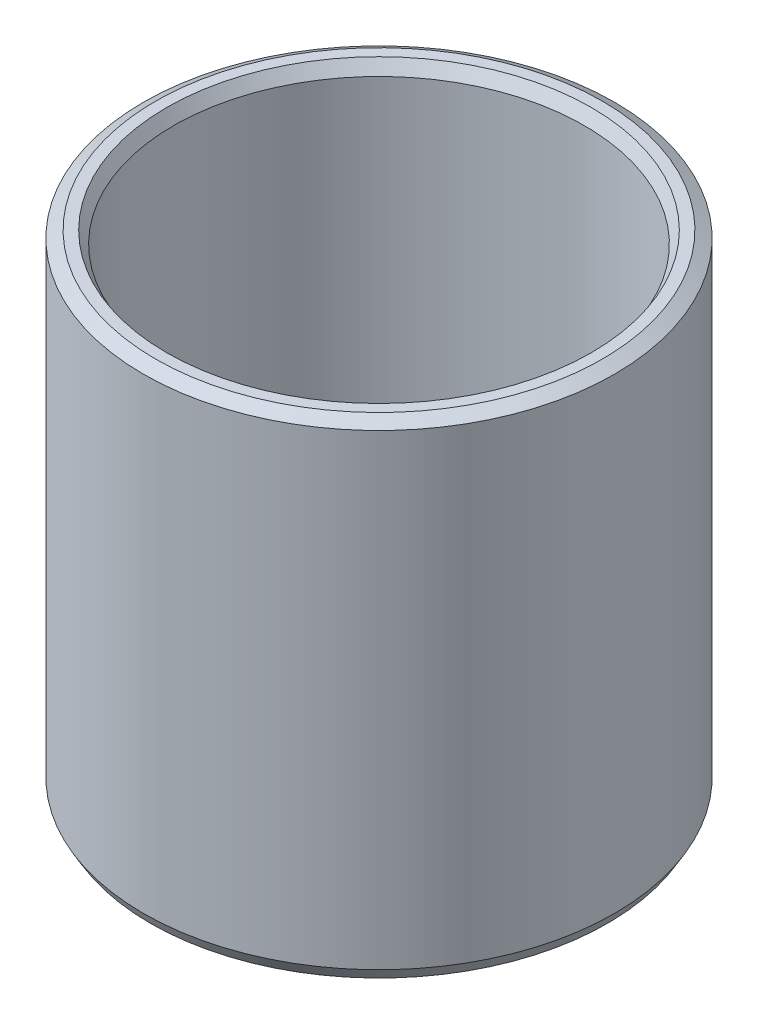
SolidWorks part; units mm, degrees
ref_plane "Front Plane" through (0, 0, 0) normal (0, 0, 1) x (1, 0, 0)
ref_plane "Top Plane" through (0, 0, 0) normal (0, 1, 0) x (1, 0, 0)
ref_plane "Right Plane" through (0, 0, 0) normal (1, 0, 0) x (0, 0, -1)
sketch "Sketch1" plane through (0, 0, 0) normal (0, 1, 0) x (1, 0, 0)
  circle A0 centre (0, 0) radius 35
  dimension "SLEEVE_OD" = 70
extrude "Boss-Extrude1" add sketch "Sketch1" along normal blind 72.234
sketch "Sketch2" plane through (0, 0, 0) normal (0, 1, 0) x (1, 0, 0)
  circle A0 centre (0, 0) radius 30.5123
  dimension "BORE_D" = 61.0247
extrude "Cut-Extrude1" cut sketch "Sketch2" along normal through all
chamfer "Chamfer1" distance 1.0428 angle 60 4 edges at (0, 72.234, 30.5123) (0, 0, 30.5123) (0, 0, 35) (0, 72.234, 35) first distance on face at (0, 72.234, 30.5123) first distance on face at (0, 0, 30.5123) first distance on face at (0, 72.234, 35)
